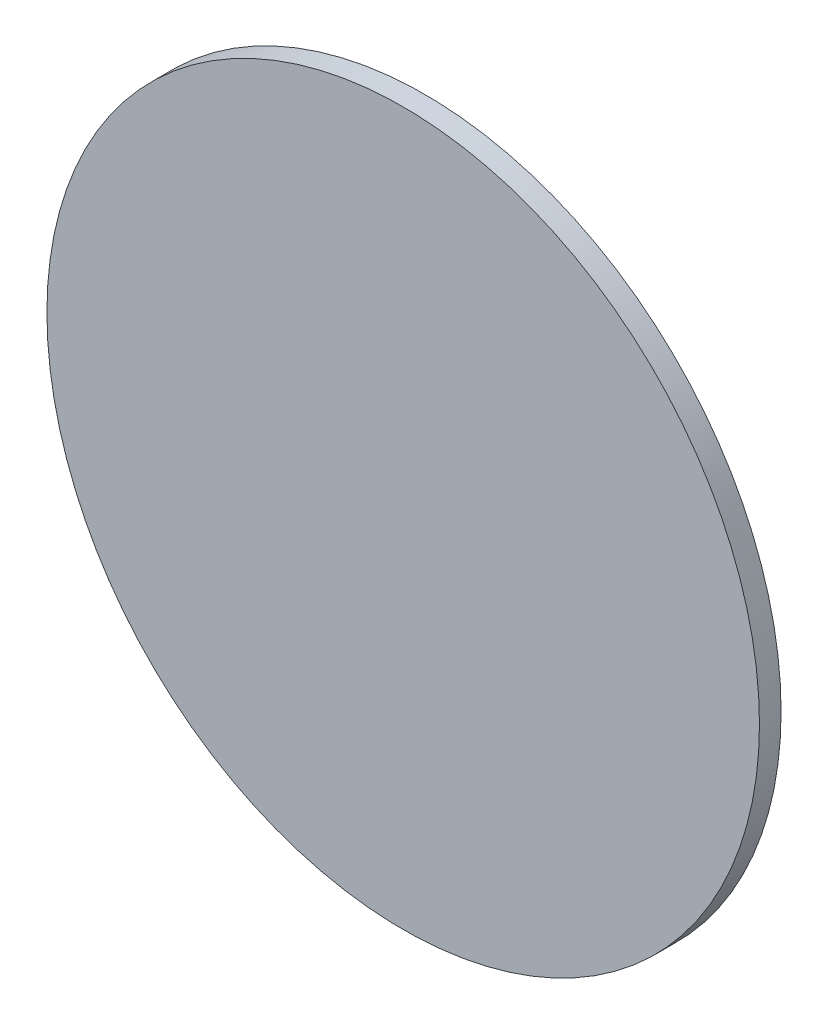
SolidWorks part; units mm, degrees
ref_plane "Alzado" through (0, 0, 0) normal (0, 0, 1) x (1, 0, 0)
ref_plane "Planta" through (0, 0, 0) normal (0, 1, 0) x (1, 0, 0)
ref_plane "Vista lateral" through (0, 0, 0) normal (1, 0, 0) x (0, 0, -1)
sketch "Croquis1" plane through (0, 0, 0) normal (0, 0, 1) x (1, 0, 0)
  circle A0 centre (0, 0) radius 82.42
  dimension "D1" = 164.84
extrude "Saliente-Extruir1" add sketch "Croquis1" along normal blind 5
sketch "Croquis3" plane through (0, 0, 5) normal (0, 0, 1) x (1, 0, 0)
  line L0 (-37.715, 72.96) -> (27.805, 72.96) construction
  line L1 (-37.715, 72.96) -> (27.805, 72.96) construction
  line L2 (27.805, 72.96) -> (27.805, -72.96)
  line L3 (-37.715, 72.96) -> (27.805, 72.96)
  line L4 (-37.715, 72.96) -> (-37.715, -72.96)
  line L5 (-37.715, -72.96) -> (27.805, -72.96)
  line L7 (-37.715, -72.96) -> (-37.715, -68.49) construction
  line L8 (-37.715, -72.96) -> (-33.115, -72.96) construction
  line L9 (-37.715, -68.49) -> (-33.115, -68.49) construction
  line L10 (-33.115, -68.49) -> (-33.115, -72.96) construction
  line L11 (-33.115, -68.49) -> (-33.115, -46.39) construction
  line L12 (-33.115, -46.39) -> (24.405, -46.39) construction
  line L13 (24.405, -46.39) -> (24.405, -68.49) construction
  line L14 (-33.115, -68.49) -> (24.405, -68.49) construction
  line L15 (-4.955, -72.96) -> (-4.955, 72.96) construction
  line L16 (-37.715, 0) -> (27.805, 0) construction
  line L17 (-33.115, 68.49) -> (-37.715, 68.49) construction
  line L18 (-33.115, 68.49) -> (-33.115, 72.96) construction
  circle A0 centre (-33.115, -68.49) radius 2.5
  circle A1 centre (-33.115, -46.39) radius 2.5
  circle A2 centre (0, 0) radius 82.1315
  circle A3 centre (24.405, -46.39) radius 2.5
  circle A4 centre (24.405, -68.49) radius 2.5
  circle A5 centre (24.405, 68.49) radius 2.5
  circle A6 centre (-33.115, 68.49) radius 2.5
  circle A7 centre (24.405, 46.39) radius 2.5
  circle A8 centre (-33.115, 46.39) radius 2.5
  dimension "D5" = 5
  dimension "D7" = 5
  dimension "D9" = 5
  dimension "D11" = 5
  dimension "D1" = 145.92
  dimension "D2" = 65.52
  dimension "D3" = 4.47
  dimension "D4" = 4.6
  dimension "D6" = 22.1
  dimension "D8" = 57.52
  dimension "D10" = 22.1
